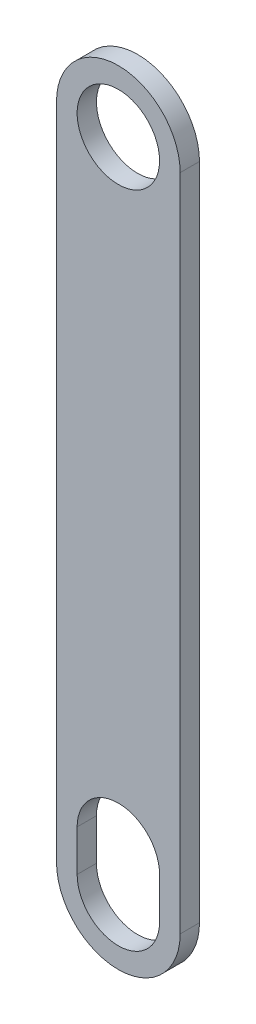
SolidWorks part; units mm, degrees
ref_plane "Front Plane" through (0, 0, 0) normal (0, 0, 1) x (1, 0, 0)
ref_plane "Top Plane" through (0, 0, 0) normal (0, 1, 0) x (1, 0, 0)
ref_plane "Right Plane" through (0, 0, 0) normal (1, 0, 0) x (0, 0, -1)
sketch "Sketch1" plane through (0, 0, 0) normal (0, 0, 1) x (1, 0, 0)
  line L0 (0, 0) -> (0, 135.4582) construction
  line L1 (-12.7, 0) -> (-12.7, 135.4582)
  line L2 (12.7, 0) -> (12.7, 135.4582)
  arc A0 (-12.7, 0) -> (12.7, 0) centre (0, 0) ccw
  arc A1 (12.7, 135.4582) -> (-12.7, 135.4582) centre (0, 135.4582) ccw
  circle A2 centre (0, 0) radius 8.4667
  circle A3 centre (0, 135.4582) radius 8.4667
  point P3 (0, 67.7291)
  dimension "D2" = 12.7
  dimension "D3" = 16.9333
  dimension "D1" = 135.4582
extrude "Boss-Extrude1" add sketch "Sketch1" along normal blind 3.9688
scale "Scale1" scale about centroid uniform scaling yes scale factor 0.75
sketch "Sketch2" plane through (0, 0, 3.4727) normal (0, 0, 1) x (1, 0, 0)
  line L0 (-6.35, 23.2759) -> (-6.35, 16.9323)
  line L1 (6.35, 16.9323) -> (6.35, 23.2759)
  line L2 (-6.35, 16.9323) -> (6.35, 16.9323)
  arc A0 (6.35, 23.2759) -> (-6.35, 23.2759) centre (0, 23.2759) ccw
  circle A1 centre (0, 118.5259) radius 6.35 construction
  circle A2 centre (0, 16.9323) radius 6.35 construction
  dimension "D1" = 95.25
extrude "Cut-Extrude1" cut sketch "Sketch2" against normal through all
